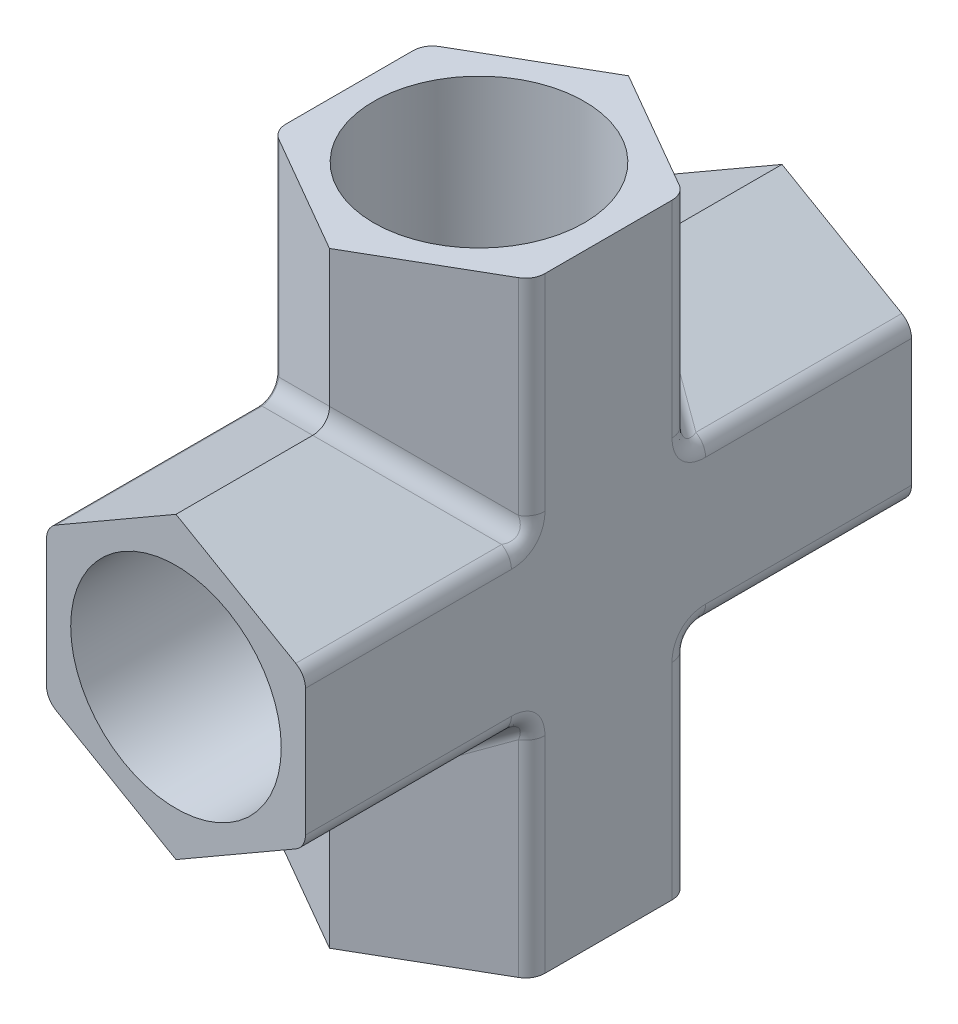
SolidWorks part; units mm, degrees
material "AISI 304"
ref_plane "Ön Düzlem" through (0, 0, 0) normal (0, 0, 1) x (1, 0, 0)
ref_plane "Üst Düzlem" through (0, 0, 0) normal (0, 1, 0) x (1, 0, 0)
ref_plane "Sağ Düzlem" through (0, 0, 0) normal (1, 0, 0) x (0, 0, -1)
sketch "Çizim1" plane through (0, 0, 0) normal (0, 0, 1) x (1, 0, 0)
  line L1 (0, -15.4441) -> (13.375, -7.7221)
  line L2 (13.375, -7.7221) -> (13.375, 7.7221)
  line L3 (13.375, 7.7221) -> (0, 15.4441)
  line L4 (0, 15.4441) -> (-13.375, 7.7221)
  line L5 (-13.375, 7.7221) -> (-13.375, -7.7221)
  line L6 (-13.375, -7.7221) -> (0, -15.4441)
  circle A0 centre (0, 0) radius 13.375 construction
  dimension "D1" = 26.75
extrude "Yükseklik-Ekstrüzyon1" add sketch "Çizim1" along normal blind 62.6
sketch "Çizim2" plane through (0, 0, 0) normal (0, 1, 0) x (1, 0, 0)
  line L0 (0, -62.6) -> (0, 0) construction
  line L1 (0, -15.8559) -> (-13.375, -23.5779)
  line L2 (-13.375, -23.5779) -> (-13.375, -39.0221)
  line L3 (-13.375, -39.0221) -> (0, -46.7441)
  line L4 (0, -46.7441) -> (13.375, -39.0221)
  line L5 (13.375, -39.0221) -> (13.375, -23.5779)
  line L6 (13.375, -23.5779) -> (0, -15.8559)
  circle A0 centre (0, -31.3) radius 13.375 construction
  dimension "D1" = 26.75
extrude "Yükseklik-Ekstrüzyon3" add sketch "Çizim2" along normal blind 31.3 and the other way blind 31.3
sketch "Çizim3" plane through (0, -31.3, 0) normal (0, -1, 0) x (1, 0, 0)
  line L0 (0, 46.7441) -> (0, 15.8559)
  circle A0 centre (0, 31.3) radius 10.875
  dimension "D1" = 21.75
extrude "Kes-Ekstrüzyon1" cut sketch "Çizim3" against normal blind 70 contours L0 A0 | L0 A0 region at (4.6155, -31.3, 31.3) region at (-4.6155, -31.3, 31.3)
sketch "Çizim4" plane through (0, 0, 62.6) normal (0, 0, 1) x (1, 0, 0)
  circle A0 centre (0, 0) radius 10.875
  dimension "D1" = 21.75
extrude "Kes-Ekstrüzyon2" cut sketch "Çizim4" against normal blind 70
fillet "Fillet1" radius 2 24 edges at (-13.375, -7.7221, 50.811) (-13.375, 7.7221, 50.811) (-13.375, 19.511, 23.5779) (-13.375, -19.511, 23.5779) (-6.6875, -11.5831, 42.8831) (-13.375, -19.511, 39.0221) (-6.6875, 11.5831, 42.8831) (-13.375, 19.511, 39.0221) (-6.6875, 11.5831, 19.7169) (-13.375, 7.7221, 11.789) (-6.6875, -11.5831, 19.7169) (-13.375, -7.7221, 11.789) (6.6875, 11.5831, 19.7169) (13.375, 7.7221, 11.789) (13.375, 19.511, 23.5779) (6.6875, 11.5831, 42.8831) (13.375, 19.511, 39.0221) (13.375, 7.7221, 50.811) (13.375, -7.7221, 50.811) (6.6875, -11.5831, 42.8831) (13.375, -19.511, 39.0221) (6.6875, -11.5831, 19.7169) (13.375, -7.7221, 11.789) (13.375, -19.511, 23.5779)
